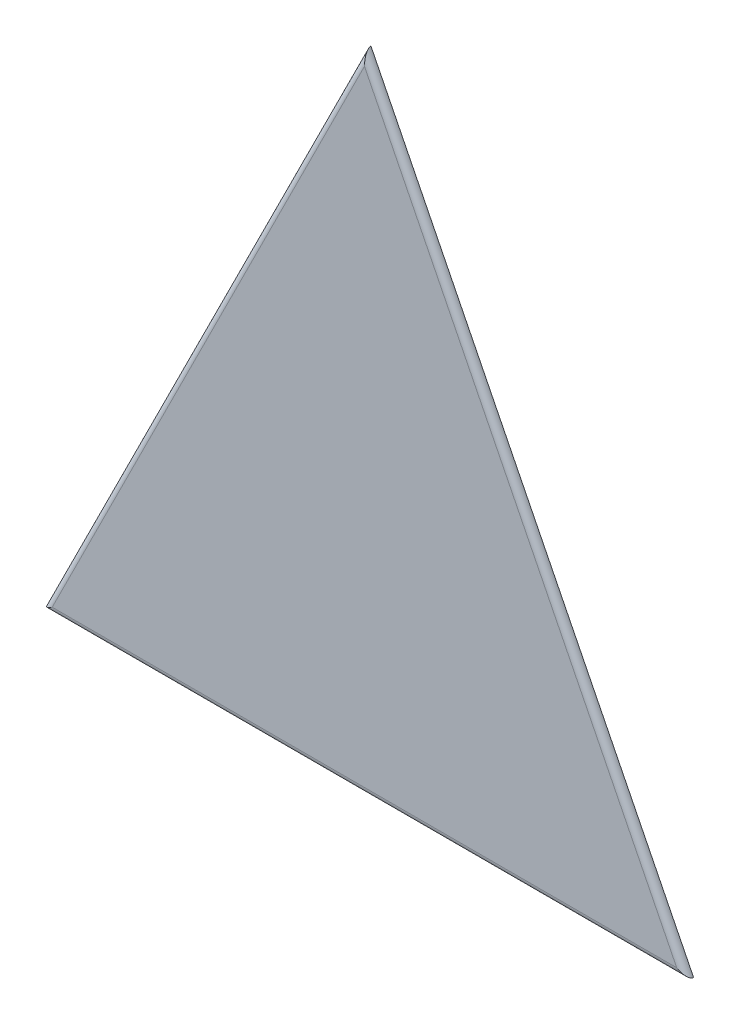
SolidWorks part; units mm, degrees
ref_plane "Front Plane" through (0, 0, 0) normal (0, 0, 1) x (1, 0, 0)
ref_plane "Top Plane" through (0, 0, 0) normal (0, 1, 0) x (1, 0, 0)
ref_plane "Right Plane" through (0, 0, 0) normal (1, 0, 0) x (0, 0, -1)
sketch "Sketch1" plane through (0, 0, 0) normal (0, 0, 1) x (1, 0, 0)
  line L0 (-50, 0) -> (50, 0)
  line L1 (50, 0) -> (0, 100)
  line L2 (0, 100) -> (-50, 0)
  line L3 (0, 200) -> (0, 0) construction
  point P5 (0, 0)
  point P6 (50.6657, 0)
  point P7 (0, 200)
  point P10 (0, 0)
  dimension "D1" = 100
  dimension "D2" = 100
extrude "Boss-Extrude1" add sketch "Sketch1" along normal blind 1
fillet "Fillet1" radius 1 3 edges at (0, 0, 1) (-25, 50, 1) (25, 50, 1)
